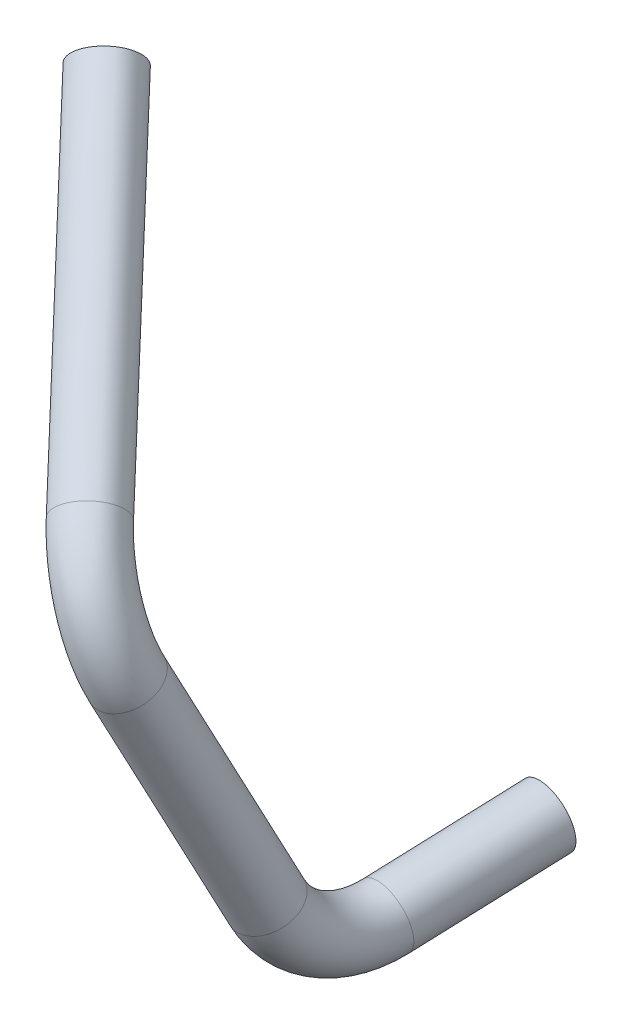
SolidWorks part; units mm, degrees
material "Plain Carbon Steel"
ref_plane "Piano frontale" through (0, 0, 0) normal (0, 0, 1) x (1, 0, 0)
ref_plane "Piano superiore" through (0, 0, 0) normal (0, 1, 0) x (1, 0, 0)
ref_plane "Piano destro" through (0, 0, 0) normal (1, 0, 0) x (0, 0, -1)
sketch3d "Schizzo3D1"
  line L0 (116.408, -1.8844, -10.3091) -> (125.3523, -9.5492, -0.639)
  line L1 (148.6933, -59.6686, -9.4769) -> (148.404, -60.0583, -7.0488)
  line L2 (125.3523, -9.5492, -0.639) -> (137.7418, -20.1663, 12.756)
  line L3 (143.2114, -30.8925, 14.4066) -> (146.5759, -54.521, 3.3996)
  line L4 (150.1771, -57.6699, -21.9305) -> (148.6933, -59.6686, -9.4769)
  arc A0 (151.3762, -58.7099, -21.9546) -> (148.978, -56.6299, -21.9065) centre (150.1771, -57.6699, -21.9305) ccw construction
  arc A4 (118.197, -0.3189, -10.723) -> (114.6191, -3.45, -9.8953) centre (116.408, -1.8844, -10.3091) ccw construction
  arc A5 (118.197, -0.3189, -10.723) -> (114.6191, -3.45, -9.8953) centre (116.408, -1.8844, -10.3091) ccw construction
  arc A6 (122.9983, -11.609, -0.0945) -> (127.7062, -7.4893, -1.1835) centre (125.3523, -9.5492, -0.639) ccw construction
  arc A7 (122.9983, -11.609, -0.0945) -> (127.7062, -7.4893, -1.1835) centre (125.3523, -9.5492, -0.639) ccw construction
  arc A8 (148.404, -60.0583, -7.0488) -> (146.5759, -54.521, 3.3996) centre (147.4151, -50.2153, -5.5869) ccw
  arc A9 (137.7418, -20.1663, 12.756) -> (143.2114, -30.8925, 14.4066) centre (137.4777, -28.1178, 6.6977) ccw
  point P4 (147.5317, -61.2333, 0.2727)
  point P5 (137.533, -51.0142, -6.8925)
  point P12 (117.8242, -3.098, -8.778)
  point P13 (117.8242, -3.098, -8.778)
  point P17 (123.4889, -7.9523, -2.6536)
  point P19 (123.4889, -7.9523, -2.6536)
  point P23 (150.3626, -57.4201, -23.4872)
  point P25 (142.232, -24.0142, 17.6107)
  point P26 (145.5701, -24.7298, 1.8982)
  dimension "D1" = 10
sweep "Sweep-Sottile1" add path "Schizzo3D1" circular profile diameter 6.35 parameters "D1"=1, "D3"=6.35
